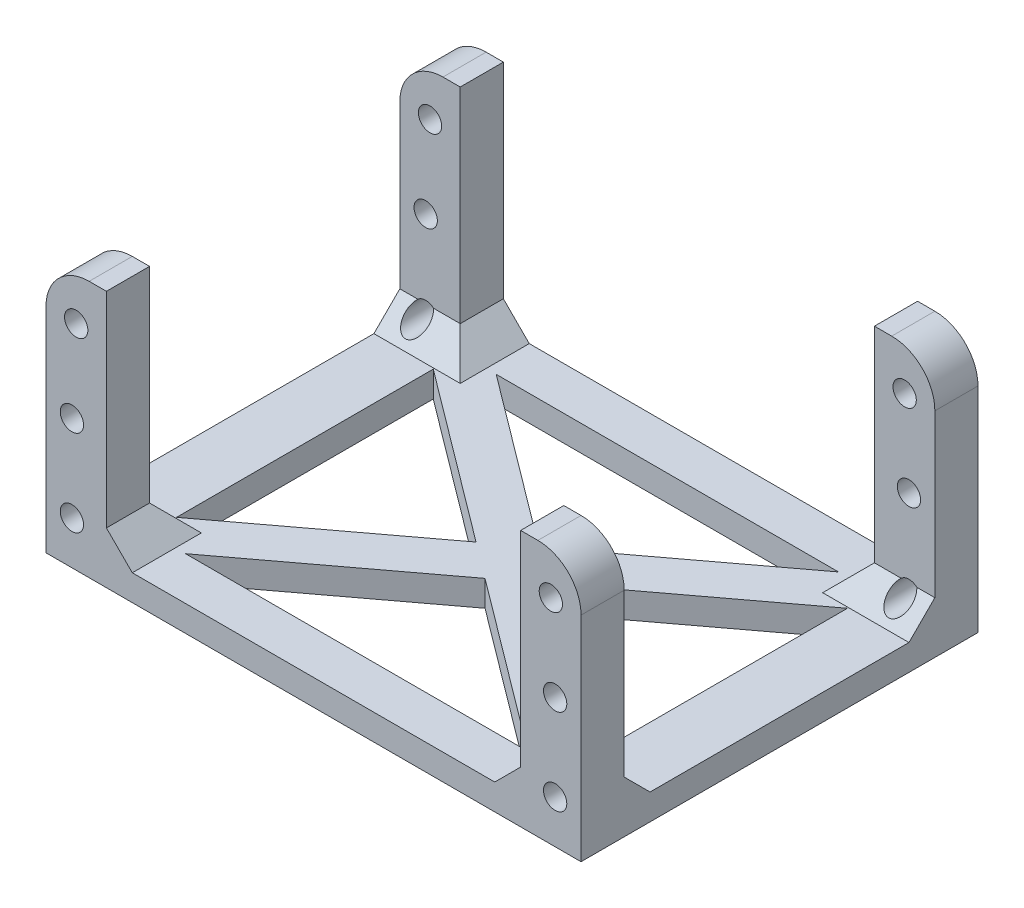
SolidWorks part; units mm, degrees
ref_plane "前视基准面" through (0, 0, 0) normal (0, 0, 1) x (1, 0, 0)
ref_plane "上视基准面" through (0, 0, 0) normal (0, 1, 0) x (1, 0, 0)
ref_plane "右视基准面" through (0, 0, 0) normal (1, 0, 0) x (0, 0, -1)
sketch "草图1" plane through (0, 0, 0) normal (0, 1, 0) x (1, 0, 0)
  line L1 (-31, -23) -> (31, -23)
  line L2 (-31, -23) -> (-31, 23)
  line L3 (-31, 23) -> (31, 23)
  line L4 (31, -23) -> (31, 23)
  line L5 (-31, -23) -> (31, 23) construction
  line L6 (-31, 23) -> (31, -23) construction
  point P0 (0, 0)
  dimension "D1" = 62
  dimension "D2" = 46
extrude "凸台-拉伸1" add sketch "草图1" along normal blind 3
sketch "草图2" plane through (0, 0, 23) normal (0, 0, 1) x (1, 0, 0)
  line L1 (-31, 3) -> (-24, 3)
  line L2 (-31, 3) -> (-31, 20)
  line L3 (-31, 20) -> (-24, 20)
  line L4 (-24, 3) -> (-24, 20)
  line L5 (31, 3) -> (24, 3)
  line L6 (31, 3) -> (31, 20)
  line L7 (31, 20) -> (24, 20)
  line L8 (24, 3) -> (24, 20)
  dimension "D1" = 17
  dimension "D2" = 7
extrude "凸台-拉伸2" add sketch "草图2" against normal blind 5
sketch "草图3" plane through (0, 0, 23) normal (0, 0, 1) x (1, 0, 0)
  line L0 (-24, 20) -> (24, 20) construction
  line L1 (0, 20) -> (0, 10) construction
  line L2 (-28, 5) -> (28, 5) construction
  line L3 (-28, 5) -> (-28, 15) construction
  line L4 (-28, 15) -> (28, 15) construction
  line L5 (28, 5) -> (28, 15) construction
  line L6 (-28, 5) -> (28, 15) construction
  line L7 (-28, 15) -> (28, 5) construction
  circle A0 centre (-28, 15) radius 1.35
  circle A1 centre (-28, 5) radius 1.35
  circle A2 centre (28, 5) radius 1.35
  circle A3 centre (28, 15) radius 1.35
  point P4 (0, 10)
  dimension "D3" = 2.7
  dimension "D1" = 10
  dimension "D2" = 56
  dimension "D4" = 10
extrude "切除-拉伸1" cut sketch "草图3" against normal blind 12
sketch "草图7" plane through (0, 20, 0) normal (0, 1, 0) x (1, 0, 0)
  line L1 (-31, -23) -> (-24, -23)
  line L2 (-31, -23) -> (-31, -18)
  line L3 (-31, -18) -> (-24, -18)
  line L4 (-24, -23) -> (-24, -18)
  line L5 (24, -23) -> (31, -23)
  line L6 (24, -23) -> (24, -18)
  line L7 (24, -18) -> (31, -18)
  line L8 (31, -23) -> (31, -18)
extrude "凸台-拉伸4" add sketch "草图7" along normal blind 9.75
sketch "草图8" plane through (0, 0, 23) normal (0, 0, 1) x (1, 0, 0)
  line L0 (-27.5, 29.75) -> (-27.5, 24.75) construction
  line L1 (-31, 29.75) -> (-24, 29.75) construction
  line L2 (27.5, 29.75) -> (27.5, 24.75) construction
  line L3 (24, 29.75) -> (31, 29.75) construction
  line L4 (-27.5, 24.75) -> (27.5, 24.75) construction
  circle A0 centre (-27.5, 24.75) radius 1.35
  circle A1 centre (27.5, 24.75) radius 1.35
  dimension "D2" = 2.7
  dimension "D1" = 5
extrude "切除-拉伸4" cut sketch "草图8" against normal up to next
mirror "镜向1" about plane through (0, 0, 0) normal (0, 0, 1) of "凸台-拉伸4", "切除-拉伸1", "凸台-拉伸2", "切除-拉伸4"
sketch "草图5" plane through (0, 29.75, 0) normal (0, 1, 0) x (1, 0, 0)
  line L1 (-24, -18) -> (24, -18)
  line L2 (-24, -18) -> (-24, 18)
  line L3 (-24, 18) -> (24, 18)
  line L4 (24, -18) -> (24, 18)
extrude "切除-拉伸3" cut sketch "草图5" against normal up to next
sketch "草图6" plane through (0, 0, 0) normal (0, 1, 0) x (1, 0, 0)
  line L0 (22.5, -20) -> (-25.5, 16)
  line L1 (22.5, -20) -> (25.5, -16)
  line L2 (-25.5, 16) -> (-22.5, 20)
  line L3 (25.5, -16) -> (-22.5, 20)
  line L4 (-24, 18) -> (24, -18) construction
  line L5 (-1.5, -2) -> (1.5, 2) construction
  line L6 (-25.5, -16) -> (22.5, 20)
  line L7 (-25.5, -16) -> (-22.5, -20)
  line L8 (22.5, 20) -> (25.5, 16)
  line L9 (-22.5, -20) -> (25.5, 16)
  line L10 (24, 18) -> (-24, -18) construction
  line L11 (-1.5, 2) -> (1.5, -2) construction
  point P1 (0, 0)
  point P2 (0, 0)
  dimension "D1" = 5
extrude "凸台-拉伸3" add sketch "草图6" along normal up to surface (3 mm away) contours L0 L6 L3 L2 | L3 L9 L8 L6 | L0 L9 L3 L6 | L7 L9 L0 L6 | L9 L0 L1 L3 region at (13.0258, 0, 9.7971) region at (-13.0258, 0, 9.7971) region at (0, 0, 0) region at (-13.0258, 0, -9.7971) region at (13.0258, 0, -9.7971) up to face at (0, 3, -20.5)
sketch "草图9" plane through (0, 0, 18) normal (0, 0, -1) x (-1, 0, 0)
  line L1 (28, 1.7091) -> (30.85, 3.3546)
  line L2 (30.85, 3.3546) -> (30.85, 6.6454)
  line L3 (30.85, 6.6454) -> (28, 8.2909)
  line L4 (28, 8.2909) -> (25.15, 6.6454)
  line L5 (25.15, 6.6454) -> (25.15, 3.3546)
  line L6 (25.15, 3.3546) -> (28, 1.7091)
  line L7 (28, 11.7091) -> (30.85, 13.3546)
  line L8 (30.85, 13.3546) -> (30.85, 16.6454)
  line L9 (30.85, 16.6454) -> (28, 18.2909)
  line L10 (28, 18.2909) -> (25.15, 16.6454)
  line L11 (25.15, 16.6454) -> (25.15, 13.3546)
  line L12 (25.15, 13.3546) -> (28, 11.7091)
  circle A0 centre (28, 5) radius 2.85 construction
  circle A1 centre (28, 15) radius 2.85 construction
  dimension "D1" = 5.7
extrude "切除-拉伸5" [suppressed] cut sketch "草图9" against normal blind 2.5 and the other way blind 5
mirror "镜向2" [suppressed] about plane through (0, 0, 0) normal (1, 0, 0)
mirror "镜向3" [suppressed] about plane through (0, 0, 0) normal (0, 0, 1)
chamfer "倒角4" distance 3 angle 45 8 edges at (-24, 3, 20.5) (24, 3, 20.5) (24, 3, -20.5) (-24, 3, -20.5) (27.5, 3, -18) (27.5, 3, 18) (-27.5, 3, 18) (-27.5, 3, -18)
fillet "圆角1" radius 5 4 edges at (31, 29.75, -20.5) (31, 29.75, 20.5) (-31, 29.75, 20.5) (-31, 29.75, -20.5)
